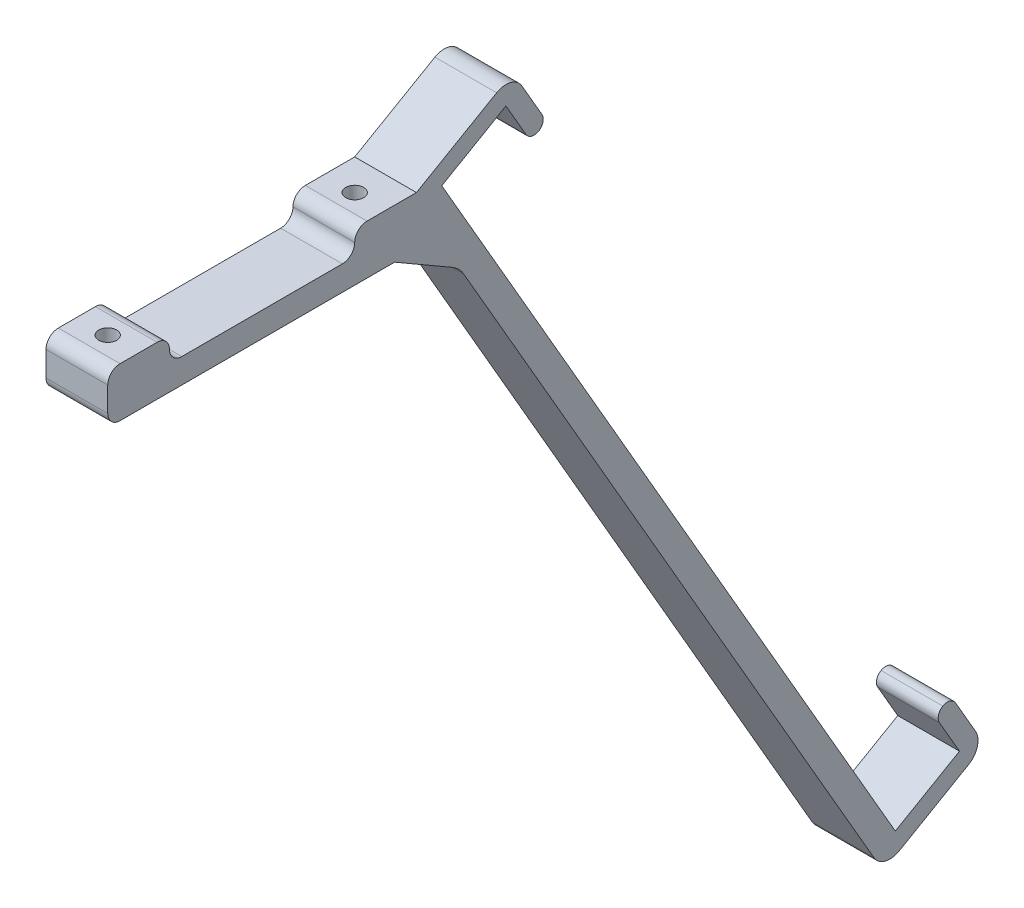
SolidWorks part; units mm, degrees
ref_plane "前视基准面" through (0, 0, 0) normal (0, 0, 1) x (1, 0, 0)
ref_plane "上视基准面" through (0, 0, 0) normal (0, 1, 0) x (1, 0, 0)
ref_plane "右视基准面" through (0, 0, 0) normal (1, 0, 0) x (0, 0, -1)
other "Configuration Table"
sketch "草图1" plane through (0, 0, 0) normal (1, 0, 0) x (0, 0, -1)
  line L0 (25, 0) -> (-25, 0)
  line L1 (25, 0) -> (98, -126.4397)
  point P4 (0, 0)
  dimension "D1" = 50
  dimension "D2" = 120
  dimension "D3" = 146
extrude "拉伸-薄壁1" add sketch "草图1" along normal blind 10 thin
sketch "草图4" plane through (10, 0, 0) normal (1, 0, 0) x (0, 0, -1)
  line L0 (27.3094, 4) -> (25, 8)
  line L1 (25, 8) -> (15, 8)
  line L2 (15, 8) -> (15, 4)
  line L3 (-25, 4) -> (27.3094, 4) construction
  line L4 (15, 4) -> (27.3094, 4)
  line L5 (-25, 4) -> (-25, 8)
  line L6 (-25, 8) -> (-15, 8)
  line L7 (-15, 8) -> (-15, 4)
  line L8 (-15, 4) -> (-25, 4)
  line L10 (27.3094, 4) -> (101.4641, -124.4397) construction
  dimension "D1" = 10
  dimension "D2" = 10
extrude "凸台-拉伸2" add sketch "草图4" against normal up to surface (10 mm away) up to face at (0, -40.4799, -33.6289)
sketch "草图2" plane through (0, 0, 0) normal (0, -1, 0) x (1, 0, 0)
  line L0 (5, 25) -> (5, -25) construction
  line L1 (10, 25) -> (0, 25) construction
  line L2 (10, -25) -> (0, -25) construction
  circle A0 centre (5, 20) radius 1.45
  circle A1 centre (5, -20) radius 1.45
  dimension "D3" = 2.9
  dimension "D1" = 40
  dimension "D2" = 5
extrude "切除-拉伸1" cut sketch "草图2" against normal up to next
fillet "圆角1" radius 2 6 edges at (5, 8, 25) (5, 4, 15) (5, 8, 15) (5, 4, -15) (5, 8, -15) (5, 0, 25)
sketch "草图6" plane through (10, 0, 0) normal (1, 0, 0) x (0, 0, -1)
  line L0 (25, 8) -> (40.5885, 17)
  line L1 (40.5885, 17) -> (46.0885, 7.4737)
  line L2 (46.0885, 7.4737) -> (43.4904, 5.9737)
  line L3 (43.4904, 5.9737) -> (39.4904, 12.9019)
  line L4 (39.4904, 12.9019) -> (26.5, 5.4019)
  line L5 (25, 8) -> (101.4641, -124.4397) construction
  line L6 (26.5, 5.4019) -> (25, 8)
  line L7 (63.2321, -58.2199) -> (59.7679, -60.2199) construction
  line L8 (25, 0) -> (98, -126.4397) construction
  line L9 (99.9641, -121.8416) -> (101.4641, -124.4397)
  line L10 (112.9545, -114.3416) -> (99.9641, -121.8416)
  line L11 (108.9545, -107.4134) -> (112.9545, -114.3416)
  line L12 (111.5526, -105.9134) -> (108.9545, -107.4134)
  line L13 (117.0526, -115.4397) -> (111.5526, -105.9134)
  line L14 (101.4641, -124.4397) -> (117.0526, -115.4397)
  dimension "D1" = 3
  dimension "D2" = 3
  dimension "D3" = 8
  dimension "D4" = 15
extrude "凸台-拉伸3" add sketch "草图6" against normal up to surface (10 mm away) up to face at (0, -13.6342, -10.9025)
fillet "圆角5" radius 1.5 4 edges at (5, -107.4134, -108.9545) (5, -105.9134, -111.5526) (5, 5.9737, -43.4904) (5, 7.4737, -46.0885)
sketch "草图7" plane through (10, 0, 0) normal (1, 0, 0) x (0, 0, -1)
  line L0 (26.5, 5.4019) -> (99.9641, -121.8416)
  line L1 (99.9641, -121.8416) -> (102.5622, -120.3416)
  line L2 (112.9545, -114.3416) -> (99.9641, -121.8416) construction
  line L3 (102.5622, -120.3416) -> (29.0981, 6.9019)
  line L4 (26.5, 5.4019) -> (39.4904, 12.9019) construction
  line L5 (29.0981, 6.9019) -> (26.5, 5.4019)
  dimension "D1" = 3
extrude "凸台-拉伸4" add sketch "草图7" against normal up to surface (10 mm away) up to face at (0, -27.3031, -38.114)
sketch "草图8" plane through (10, 0, 0) normal (1, 0, 0) x (0, 0, -1)
  line L0 (25, 0) -> (98, -126.4397)
  line L1 (98, -126.4397) -> (100.5981, -124.9397)
  line L2 (117.0526, -115.4397) -> (98, -126.4397) construction
  line L3 (100.5981, -124.9397) -> (28.4641, 0)
  line L5 (102.5622, -120.3416) -> (29.0981, 6.9019) construction
  line L6 (25, 0) -> (28.4641, 0)
  dimension "D1" = 4
extrude "切除-拉伸3" cut sketch "草图8" against normal up to next
fillet "圆角3" radius 3 3 edges at (5, -115.4397, -117.0526) (5, 17, -40.5885) (5, -124.9397, -100.5981)
chamfer "倒角1" distance 7 1 edges at (5, 0, -28.4641)
fillet "圆角7" radius 5 1 edges at (5, -6.0622, -31.9641)
